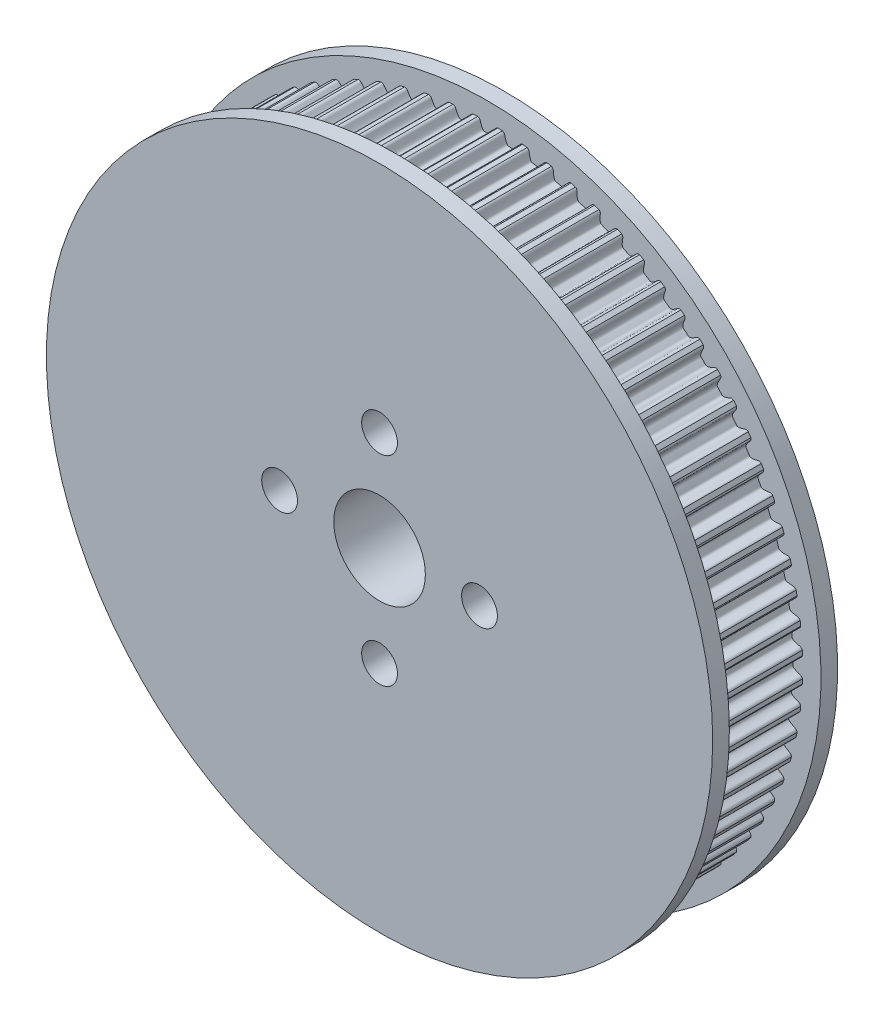
SolidWorks part; units mm, degrees
ref_plane "前视基准面" through (0, 0, 0) normal (0, 0, 1) x (1, 0, 0)
ref_plane "上视基准面" through (0, 0, 0) normal (0, 1, 0) x (1, 0, 0)
ref_plane "右视基准面" through (0, 0, 0) normal (1, 0, 0) x (0, 0, -1)
other "Configuration Table"
ref_axis "基准轴1" through (0, 0, 55) along (0, 0, -1)
sketch "SketchRevolveGearBelt01" plane through (0, 0, 0) normal (1, 0, 0) x (0, 0, -1)
  line L0 (0, 0) -> (1, 0) construction
  line L1 (9.774, 0) -> (9.774, 35.7972)
  line L2 (9.774, 35.7972) -> (9.012, 35.7972)
  line L3 (9.012, 35.7972) -> (9.012, 38.0456)
  line L4 (9.012, 38.0456) -> (9.48, 39.1756)
  line L5 (9.48, 39.1756) -> (8.7761, 39.4672)
  line L6 (8.7761, 39.4672) -> (8.25, 38.1972)
  line L7 (8.25, 38.1972) -> (8.25, 37.8022)
  line L8 (8.25, 37.8022) -> (-8.25, 37.8022)
  line L9 (-8.25, 37.8022) -> (-8.25, 38.1972)
  line L10 (-8.25, 38.1972) -> (-8.7761, 39.4672)
  line L11 (-8.7761, 39.4672) -> (-9.48, 39.1756)
  line L12 (-9.48, 39.1756) -> (-9.012, 38.0456)
  line L13 (-9.012, 38.0456) -> (-9.012, 35.7972)
  line L14 (-9.012, 35.7972) -> (-9.774, 35.7972)
  line L15 (-9.774, 35.7972) -> (-9.774, 0)
  line L16 (-9.774, 0) -> (9.774, 0)
  dimension "GearBeltFlange1OutsideLength" = 2.2484
  dimension "GearBeltFlange1X" = 0.468
  dimension "GearBeltFlange1Y" = 1.13
  dimension "GearBeltFlangeThickness" = 0.762
  dimension "GearBeltFlangeInside" = 0.395
  dimension "GearBeltOutsideDiameter" = 37.8022
  dimension "GearBeltFlange2X" = 0.468
revolve "Gates_PowerGrip_GT_3mm, 15mm Belt Width" add sketch "SketchRevolveGearBelt01" angle 360 about L0
sketch "SketchToothGearBelt01" plane through (0, 0, 0) normal (0, 0, 1) x (1, 0, 0)
  arc A0 (37.7936, 1.2905) -> (37.7936, -1.2905) centre (0, 0) cw
  spline S0 degree 3 poles (37.7936, -1.2905) (37.7931, -1.265) (37.7886, -1.2268) (37.7756, -1.1774) (37.7623, -1.1415) (37.7456, -1.107) (37.7257, -1.0743) (37.7028, -1.0436) (37.6771, -1.0152) (37.6487, -0.9894) (37.6181, -0.9665) (37.5853, -0.9466) (37.5509, -0.9298) (37.4851, -0.9065) (37.4027, -0.8817) (37.3064, -0.8512) (37.2277, -0.8247) (37.1538, -0.7983) (37.0846, -0.7718) (37.0202, -0.7454) (36.9606, -0.7189) (36.9057, -0.6925) (36.8556, -0.666) (36.8102, -0.6396) (36.7695, -0.6131) (36.7336, -0.5867) (36.7025, -0.5602) (36.676, -0.5337) (36.6543, -0.5071) (36.6374, -0.4805) (36.6252, -0.4538) (36.6177, -0.4269) (36.6144, -0.3755) (36.6191, -0.3) (36.6194, -0.2) (36.6205, -0.1) (36.6207, 0) (36.6205, 0.1) (36.6194, 0.2) (36.6191, 0.3) (36.6144, 0.3755) (36.6177, 0.4269) (36.6252, 0.4538) (36.6374, 0.4805) (36.6543, 0.5071) (36.676, 0.5337) (36.7025, 0.5602) (36.7336, 0.5867) (36.7695, 0.6131) (36.8102, 0.6396) (36.8556, 0.666) (36.9057, 0.6925) (36.9606, 0.7189) (37.0202, 0.7454) (37.0846, 0.7718) (37.1538, 0.7983) (37.2277, 0.8247) (37.3064, 0.8512) (37.4027, 0.8817) (37.4851, 0.9065) (37.5509, 0.9298) (37.5853, 0.9466) (37.6181, 0.9665) (37.6487, 0.9894) (37.6771, 1.0152) (37.7028, 1.0436) (37.7257, 1.0743) (37.7456, 1.107) (37.7623, 1.1415) (37.7756, 1.1774) (37.7886, 1.2268) (37.7931, 1.265) (37.7936, 1.2905) knots 0 0 0 0 0.019345 0.029017 0.03869 0.048362 0.058034 0.067707 0.077379 0.087051 0.096724 0.106396 0.116069 0.125741 0.159263 0.181399 0.202388 0.222239 0.240959 0.258559 0.275051 0.290449 0.304771 0.31804 0.330284 0.341538 0.351849 0.361276 0.369898 0.377817 0.385165 0.392107 0.398835 0.424145 0.44943 0.474715 0.5 0.525285 0.55057 0.575855 0.601165 0.607893 0.614835 0.622183 0.630102 0.638724 0.648151 0.658462 0.669716 0.68196 0.695229 0.709551 0.724949 0.741441 0.759041 0.777761 0.797612 0.818601 0.840737 0.874259 0.883931 0.893604 0.903276 0.912949 0.922621 0.932293 0.941966 0.951638 0.96131 0.970983 0.980655 1 1 1 1
extrude "ToothExtrudeCutGearBelt01" cut sketch "SketchToothGearBelt01" against normal blind 8.25 and the other way blind 8.25
pattern_circular "Tooth Pattern, 80" count 80 every 4.5 about axis through (0, 0, 55) along (0, 0, -1) of "ToothExtrudeCutGearBelt01"
sketch "BoreRevolveSketch" plane through (0, 0, 0) normal (1, 0, 0) x (0, 0, -1)
  line L0 (0, 0) -> (1, 0) construction
  line L1 (-9.774, 0) -> (9.774, 0)
  line L2 (9.774, 0) -> (9.774, 5)
  line L3 (9.774, 5) -> (-9.774, 5)
  line L4 (-9.774, 5) -> (-9.774, 0)
  dimension "TaperSide1" = 5
  dimension "TaperSide2" = 5
revolve "BoreRevolveCut" cut sketch "BoreRevolveSketch" angle 360 about L0
sketch "AuxiliarySketchGearBelt01" plane through (0, 0, 0) normal (0, 0, 1) x (1, 0, 0)
  circle A0 centre (0, 0) radius 38.1972 construction
  dimension "PitchDiameter" = 76.3944
sketch "草图5" plane through (0, 0, 9.774) normal (0, 0, 1) x (1, 0, 0)
  circle A0 centre (0, 0) radius 51.1436
extrude "切除-拉伸2" cut sketch "草图5" against normal blind 4.55
sketch "草图6" plane through (0, 0, -9.774) normal (0, 0, -1) x (-1, 0, 0)
  circle A0 centre (0, 0) radius 46.5593
extrude "切除-拉伸3" cut sketch "草图6" against normal blind 4
sketch "草图7" plane through (0, 0, -5.774) normal (0, 0, -1) x (-1, 0, 0)
  circle A0 centre (0, 0) radius 40
  dimension "D1" = 80
extrude "凸台-拉伸1" add sketch "草图7" along normal blind 2
sketch "草图8" plane through (0, 0, 5.224) normal (0, 0, 1) x (1, 0, 0)
  circle A0 centre (0, 0) radius 40
extrude "凸台-拉伸2" add sketch "草图8" along normal blind 2
sketch "草图9" plane through (0, 0, 7.224) normal (0, 0, 1) x (1, 0, 0)
  circle A0 centre (0, 0) radius 5.5
  circle A2 centre (0, 12) radius 2.15
  circle A3 centre (12, 0) radius 2.15
  circle A4 centre (0, -12) radius 2.15
  circle A5 centre (-12, 0) radius 2.15
  point P15 (0, 0)
  dimension "D1" = 11
  dimension "D3" = 4.3
  dimension "D4" = 4
extrude "切除-拉伸4" cut sketch "草图9" against normal through all
sketch "草图10" plane through (0, 0, -7.774) normal (0, 0, -1) x (-1, 0, 0)
  circle A0 centre (0, 0) radius 16.5
  dimension "D1" = 33
extrude "切除-拉伸5" cut sketch "草图10" against normal blind 2
